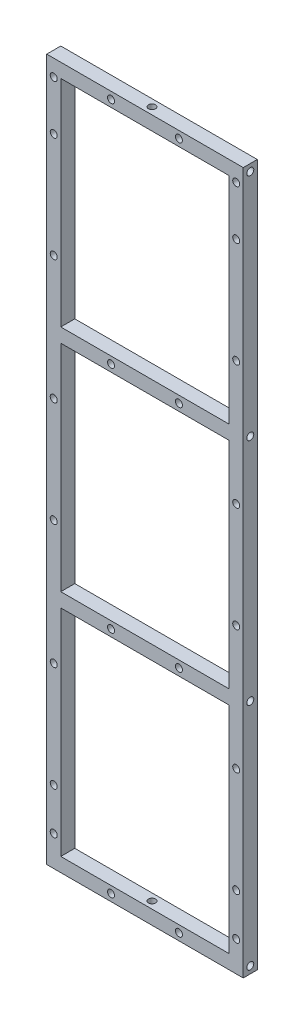
SolidWorks part; units mm, degrees
ref_plane "Front Plane" through (0, 0, 0) normal (0, 0, 1) x (1, 0, 0)
ref_plane "Top Plane" through (0, 0, 0) normal (0, 1, 0) x (1, 0, 0)
ref_plane "Right Plane" through (0, 0, 0) normal (1, 0, 0) x (0, 0, -1)
sketch "Sketch1" plane through (0, 0, 0) normal (0, 0, 1) x (1, 0, 0)
  line L0 (36, 144) -> (36, 52)
  line L9 (-42, -150) -> (42, -150)
  line L10 (-42, -150) -> (-42, 150)
  line L11 (-42, 150) -> (42, 150)
  line L12 (42, -150) -> (42, 150)
  line L15 (-36, -144) -> (36, -144)
  line L16 (-36, -144) -> (-36, -52)
  line L17 (-36, 144) -> (36, 144)
  line L21 (-36, 52) -> (36, 52)
  line L23 (-36, 46) -> (36, 46)
  line L25 (-36, -46) -> (36, -46)
  line L27 (-36, -52) -> (36, -52)
  line L33 (36, 46) -> (36, -46)
  line L34 (-36, 52) -> (-36, 144)
  line L35 (-36, -46) -> (-36, 46)
  line L36 (36, -52) -> (36, -144)
  point P0 (0, 0)
  point P4 (0, -46)
  point P6 (0, 0)
  point P20 (0, 0)
  point P21 (0, -150)
  dimension "D1" = 84
  dimension "D2" = 300
  dimension "D3" = 72
  dimension "D4" = 288
  dimension "D5" = 6
  dimension "D6" = 92
  dimension "D7" = 6
  dimension "D8" = 92
  dimension "D9" = 6
  dimension "D10" = 6
  dimension "D11" = 92
extrude "Boss-Extrude1" add sketch "Sketch1" along normal blind 6
sketch "Sketch2" plane through (42, 0, 0) normal (1, 0, 0) x (0, 0, -1)
  line L0 (-6, 150) -> (0, 150) construction
  circle A0 centre (-3, 147) radius 1.5
  circle A1 centre (-3, 49) radius 1.5
  circle A2 centre (-3, -49) radius 1.5
  circle A3 centre (-3, -147) radius 1.5
  dimension "D1" = 3
  dimension "D2" = 4
extrude "Cut-Extrude1" cut sketch "Sketch2" against normal blind 10
mirror "Mirror1" about plane through (0, 0, 0) normal (1, 0, 0) of "Cut-Extrude1"
sketch "Sketch3" plane through (0, 0, 6) normal (0, 0, 1) x (1, 0, 0)
  line L0 (-42, 150) -> (42, 150) construction
  line L1 (-42, -150) -> (-42, 150) construction
  circle A0 centre (-39, 143) radius 1.5
  circle A1 centre (39, 143) radius 1.5
  circle A2 centre (39, -137) radius 1.5
  circle A3 centre (-39, -137) radius 1.5
  dimension "D1" = 7
  dimension "D2" = 3
  dimension "D3" = 2
  dimension "D4" = 2
extrude "Cut-Extrude2" cut sketch "Sketch3" against normal blind 10
sketch "Sketch4" plane through (0, 0, 6) normal (0, 0, 1) x (1, 0, 0)
  line L0 (-42, -150) -> (-42, 150) construction
  line L1 (42, -150) -> (42, 150) construction
  line L2 (-42, 150) -> (42, 150) construction
  circle A0 centre (-14.5, 147) radius 1.5
  circle A1 centre (14.5, 147) radius 1.5
  circle A2 centre (14.5, 49) radius 1.5
  circle A3 centre (-14.5, 49) radius 1.5
  circle A4 centre (14.5, -49) radius 1.5
  circle A5 centre (-14.5, -49) radius 1.5
  circle A6 centre (14.5, -147) radius 1.5
  circle A7 centre (-14.5, -147) radius 1.5
  circle A8 centre (-39, 122) radius 1.5
  circle A9 centre (-39, 77) radius 1.5
  circle A10 centre (39, 122) radius 1.5
  circle A11 centre (39, 77) radius 1.5
  circle A12 centre (39, 24) radius 1.5
  circle A13 centre (39, -21) radius 1.5
  circle A14 centre (39, -74) radius 1.5
  circle A15 centre (39, -119) radius 1.5
  circle A16 centre (-39, 24) radius 1.5
  circle A17 centre (-39, -21) radius 1.5
  circle A18 centre (-39, -74) radius 1.5
  circle A19 centre (-39, -119) radius 1.5
  dimension "D1" = 27.5
  dimension "D4" = 45
  dimension "D7" = 2
  dimension "D2" = 27.5
  dimension "D3" = 4
  dimension "D5" = 28
  dimension "D6" = 28
  dimension "D9" = 3
  dimension "D8" = 3
extrude "Cut-Extrude3" cut sketch "Sketch4" against normal blind 10
sketch "Sketch5" plane through (0, 150, 0) normal (0, 1, 0) x (1, 0, 0)
  line L0 (42, -6) -> (-42, -6) construction
  circle A0 centre (0, -3) radius 1.5
  point P5 (0, -6)
  dimension "D1" = 3
extrude "Cut-Extrude4" cut sketch "Sketch5" against normal blind 10
mirror "Mirror2" about plane through (0, 0, 0) normal (0, 1, 0) of "Cut-Extrude4"
